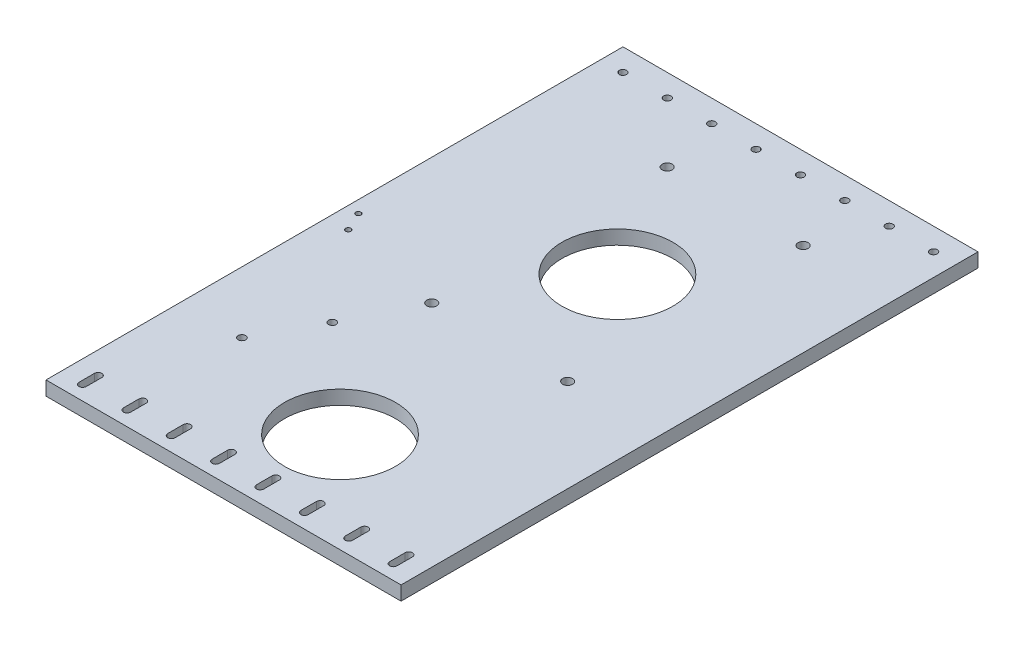
SolidWorks part; units mm, degrees
material "6061 Alloy"
ref_plane "Front Plane" through (0, 0, 0) normal (0, 0, 1) x (1, 0, 0)
ref_plane "Top Plane" through (0, 0, 0) normal (0, 1, 0) x (1, 0, 0)
ref_plane "Right Plane" through (0, 0, 0) normal (1, 0, 0) x (0, 0, -1)
sketch "Sketch1" plane through (0, 0, 0) normal (0, 1, 0) x (1, 0, 0)
  line L0 (87.5, 260) -> (87.5, 0) construction
  line L1 (0, 0) -> (160, 0)
  line L2 (0, 0) -> (0, 260)
  line L3 (0, 260) -> (160, 260)
  line L4 (160, 0) -> (160, 260)
  line L5 (56.875, 223.0441) -> (118.125, 223.0441) construction
  line L6 (10, 6.5) -> (10, 13.5) construction
  line L7 (5.4755, 135.2989) -> (9.5163, 126.7011) construction
  line L8 (22, 0) -> (22, 260) construction
  line L9 (22, 136) -> (0, 136) construction
  line L10 (22, 126) -> (0, 126) construction
  line L11 (0, 136) -> (0, 126) construction
  line L12 (17.3003, 136) -> (22, 126) construction
  line L13 (8.35, 6.5) -> (8.35, 13.5)
  line L14 (11.65, 6.5) -> (11.65, 13.5)
  line L15 (10, 250) -> (10, 0) construction
  line L16 (31.65, 6.5) -> (31.65, 13.5)
  line L17 (28.35, 6.5) -> (28.35, 13.5)
  line L18 (30, 6.5) -> (30, 13.5) construction
  line L19 (51.65, 6.5) -> (51.65, 13.5)
  line L20 (48.35, 6.5) -> (48.35, 13.5)
  line L21 (50, 6.5) -> (50, 13.5) construction
  line L22 (71.65, 6.5) -> (71.65, 13.5)
  line L23 (68.35, 6.5) -> (68.35, 13.5)
  line L24 (70, 6.5) -> (70, 13.5) construction
  line L25 (91.65, 6.5) -> (91.65, 13.5)
  line L26 (88.35, 6.5) -> (88.35, 13.5)
  line L27 (90, 6.5) -> (90, 13.5) construction
  line L28 (111.65, 6.5) -> (111.65, 13.5)
  line L29 (108.35, 6.5) -> (108.35, 13.5)
  line L30 (110, 6.5) -> (110, 13.5) construction
  line L31 (131.65, 6.5) -> (131.65, 13.5)
  line L32 (128.35, 6.5) -> (128.35, 13.5)
  line L33 (130, 6.5) -> (130, 13.5) construction
  line L34 (151.65, 6.5) -> (151.65, 13.5)
  line L35 (148.35, 6.5) -> (148.35, 13.5)
  line L36 (150, 6.5) -> (150, 13.5) construction
  line L37 (10, 250) -> (30, 250) construction
  line L38 (118.125, 223.0441) -> (118.125, 116.9559) construction
  line L39 (118.125, 116.9559) -> (56.875, 116.9559) construction
  line L40 (56.875, 116.9559) -> (56.875, 223.0441) construction
  circle A0 centre (87.5, 170) radius 25
  circle A1 centre (87.5, 45) radius 25
  circle A2 centre (87.5, 170) radius 61.25 construction
  circle A4 centre (118.125, 116.9559) radius 2.25
  circle A5 centre (56.875, 116.9559) radius 2.25
  circle A7 centre (56.875, 223.0441) radius 2.25
  circle A8 centre (118.125, 223.0441) radius 2.25
  circle A10 centre (5.4755, 135.2989) radius 1.175
  circle A11 centre (9.5163, 126.7011) radius 1.175
  circle A12 centre (87.5, 170) radius 78 construction
  circle A13 centre (10, 250) radius 1.65
  arc A14 (8.35, 6.5) -> (11.65, 6.5) centre (10, 6.5) ccw
  arc A15 (11.65, 13.5) -> (8.35, 13.5) centre (10, 13.5) ccw
  circle A16 centre (30, 250) radius 1.65
  arc A17 (28.35, 6.5) -> (31.65, 6.5) centre (30, 6.5) ccw
  arc A18 (31.65, 13.5) -> (28.35, 13.5) centre (30, 13.5) ccw
  circle A19 centre (50, 250) radius 1.65
  arc A20 (48.35, 6.5) -> (51.65, 6.5) centre (50, 6.5) ccw
  arc A21 (51.65, 13.5) -> (48.35, 13.5) centre (50, 13.5) ccw
  circle A22 centre (70, 250) radius 1.65
  arc A23 (68.35, 6.5) -> (71.65, 6.5) centre (70, 6.5) ccw
  arc A24 (71.65, 13.5) -> (68.35, 13.5) centre (70, 13.5) ccw
  circle A25 centre (90, 250) radius 1.65
  arc A26 (88.35, 6.5) -> (91.65, 6.5) centre (90, 6.5) ccw
  arc A27 (91.65, 13.5) -> (88.35, 13.5) centre (90, 13.5) ccw
  circle A28 centre (110, 250) radius 1.65
  arc A29 (108.35, 6.5) -> (111.65, 6.5) centre (110, 6.5) ccw
  arc A30 (111.65, 13.5) -> (108.35, 13.5) centre (110, 13.5) ccw
  circle A31 centre (130, 250) radius 1.65
  arc A32 (128.35, 6.5) -> (131.65, 6.5) centre (130, 6.5) ccw
  arc A33 (131.65, 13.5) -> (128.35, 13.5) centre (130, 13.5) ccw
  circle A34 centre (150, 250) radius 1.65
  arc A35 (148.35, 6.5) -> (151.65, 6.5) centre (150, 6.5) ccw
  arc A36 (151.65, 13.5) -> (148.35, 13.5) centre (150, 13.5) ccw
  point P12 (0, 0)
  point P15 (87.5, 170)
  point P29 (10, 10)
  point P42 (7.4959, 131)
  point P43 (0, 131)
  point P55 (30, 10)
  point P65 (50, 10)
  point P74 (70, 10)
  point P83 (90, 10)
  point P92 (110, 10)
  point P101 (130, 10)
  point P110 (150, 10)
  dimension "D3" = 50
  dimension "D4" = 50
  dimension "D7" = 122.5
  dimension "D8" = 4.5
  dimension "D11" = 124
  dimension "D13" = 2.35
  dimension "D16" = 156
  dimension "D19" = 3.3
  dimension "D24" = 240
  dimension "D27" = 106.0881
  dimension "D1" = 160
  dimension "D2" = 260
  dimension "D5" = 125
  dimension "D6" = 90
  dimension "D10" = 56.875
  dimension "D12" = 65.5
  dimension "D14" = 9.5
  dimension "D15" = 10
  dimension "D17" = 11
  dimension "D18" = 72.5
  dimension "D20" = 10
  dimension "D21" = 10
  dimension "D22" = 3.3
  dimension "D23" = 7
  dimension "D26" = 20
  dimension "D9" = 36.9559
  dimension "D25" = 8
extrude "Boss-Extrude1" add sketch "Sketch1" along normal blind 6.35 contours A1 | A0 | A4 | A8 | A7 | L4 L3 L2 L1 | A5 | A11 | A10 | A28 | A25 | A31 | A34 | A22 | A19 | A16 | A13 | L14 A15 L13 A14 | L16 A18 L17 A17 | L19 A21 L20 A20 | L22 A24 L23 A23 | L25 A27 L26 A26 | L28 A30 L29 A29 | L31 A33 L32 A32 | L34 A36 L35 A35 region at (87.5, 0, -170) region at (87.5, 0, -45) region at (118.125, 0, -116.9559) region at (56.875, 0, -223.0441) region at (118.125, 0, -223.0441)
sketch "Sketch2" plane through (0, 6.35, 0) normal (0, 1, 0) x (1, 0, 0)
  line L0 (27.6639, 60.641) -> (42.0639, 86.959) construction
  line L1 (87.5, 170) -> (42.0639, 86.959) construction
  line L2 (34.8639, 73.8) -> (87.5, 45) construction
  circle A0 centre (27.6639, 60.641) radius 1.7
  circle A1 centre (42.0639, 86.959) radius 1.7
  dimension "D1" = 3.4
  dimension "D2" = 30
  dimension "D3" = 60
extrude "Cut-Extrude1" cut sketch "Sketch2" against normal through all
